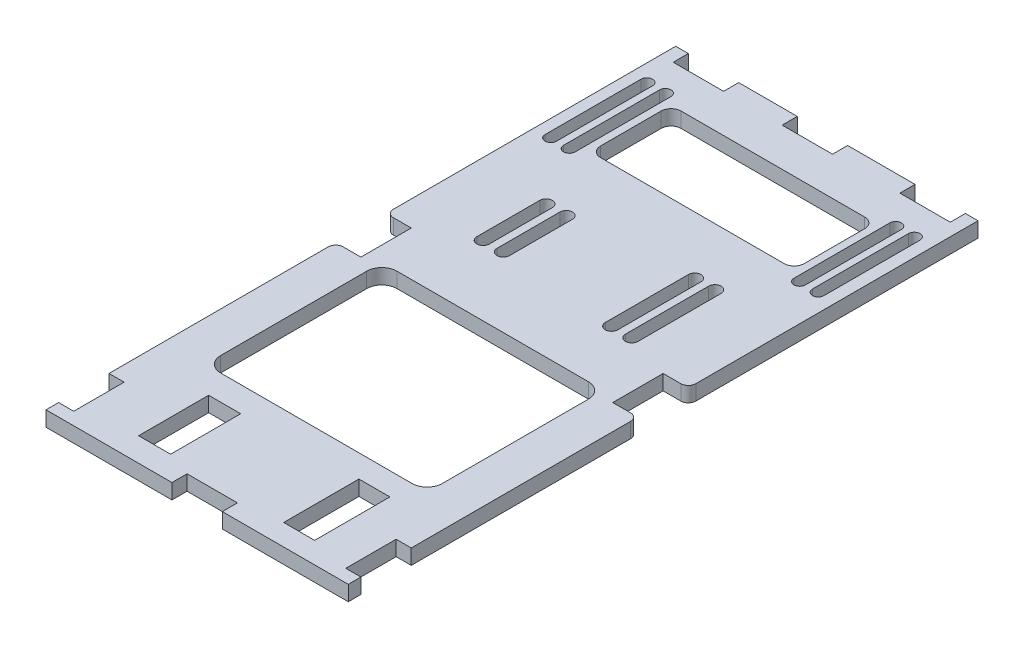
SolidWorks part; units mm, degrees
material "Acrílico (Impacto medio-alto)"
ref_plane "Alzado" through (0, 0, 0) normal (0, 0, 1) x (1, 0, 0)
ref_plane "Planta" through (0, 0, 0) normal (0, 1, 0) x (1, 0, 0)
ref_plane "Vista lateral" through (0, 0, 0) normal (1, 0, 0) x (0, 0, -1)
sketch "Croquis1" plane through (0, 0, 0) normal (0, 1, 0) x (1, 0, 0)
  line L0 (19.1085, -58.278) -> (19.1085, -43.3424) construction
  line L1 (-30, 62.5) -> (-27.5, 62.5)
  line L2 (-30, 62.5) -> (-30, 6.5)
  line L3 (-30, -62.5) -> (-5, -62.5)
  line L4 (30, 62.5) -> (30, 6.5)
  line L5 (-30, 62.5) -> (30, -62.5) construction
  line L6 (-30, -62.5) -> (30, 62.5) construction
  line L7 (19.1085, -43.3424) -> (12.9586, -43.3424) construction
  line L8 (12.9586, -43.3424) -> (12.9586, -58.278) construction
  line L9 (12.9586, -58.278) -> (19.1085, -58.278) construction
  line L10 (-16.3572, -43.8549) -> (-16.3572, -57.7655) construction
  line L11 (-16.3572, -57.7655) -> (-10, -57.7655) construction
  line L12 (-10, -43.8549) -> (-16.3572, -43.8549) construction
  line L13 (-10, -57.7655) -> (-10, -43.8549) construction
  line L14 (19.1085, -58.278) -> (19.1085, -43.3424)
  line L15 (19.1085, -43.3424) -> (12.9586, -43.3424)
  line L16 (12.9586, -43.3424) -> (12.9586, -58.278)
  line L17 (12.9586, -58.278) -> (19.1085, -58.278)
  line L18 (-16.3572, -43.8549) -> (-16.3572, -57.7655)
  line L19 (-16.3572, -57.7655) -> (-10, -57.7655)
  line L20 (-10, -43.8549) -> (-16.3572, -43.8549)
  line L21 (-10, -57.7655) -> (-10, -43.8549)
  line L22 (5, -59.5) -> (5, -62.5) construction
  line L23 (-5, -59.5) -> (-5, -62.5) construction
  line L24 (-5, -59.5) -> (5, -59.5) construction
  line L25 (5, -59.5) -> (5, -62.5)
  line L26 (-5, -59.5) -> (-5, -62.5)
  line L27 (-5, -59.5) -> (5, -59.5)
  line L28 (5, -62.5) -> (30, -62.5)
  line L29 (27.5, 59.5) -> (27.5, 62.5) construction
  line L30 (27.5, 59.5) -> (17.5, 59.5) construction
  line L31 (17.5, 59.5) -> (17.5, 62.5) construction
  line L32 (-17.5, 62.5) -> (-17.5, 59.5) construction
  line L33 (-27.5, 59.5) -> (-17.5, 59.5) construction
  line L34 (-27.5, 62.5) -> (-27.5, 59.5) construction
  line L35 (-25, 5) -> (-25, -5) construction
  line L36 (-25, -5) -> (-30, -5) construction
  line L37 (-30, 5) -> (-25, 5) construction
  line L38 (30, -5) -> (25, -5) construction
  line L39 (25, 5) -> (25, -5) construction
  line L40 (25, 5) -> (30, 5) construction
  line L41 (27.5, 59.5) -> (27.5, 62.5)
  line L42 (27.5, 59.5) -> (17.5, 59.5)
  line L43 (17.5, 59.5) -> (17.5, 62.5)
  line L44 (-17.5, 62.5) -> (-17.5, 59.5)
  line L45 (-27.5, 59.5) -> (-17.5, 59.5)
  line L46 (-27.5, 62.5) -> (-27.5, 59.5)
  line L47 (-25, 5) -> (-25, -5)
  line L48 (-25, -5) -> (-28.5, -5)
  line L49 (-28.5, 5) -> (-25, 5)
  line L50 (28.5, -5) -> (25, -5)
  line L51 (25, 5) -> (25, -5)
  line L52 (25, 5) -> (28.5, 5)
  line L53 (-17.5, 62.5) -> (-5.876, 62.5)
  line L54 (27.5, 62.5) -> (30, 62.5)
  line L55 (-30, -6.5) -> (-30, -50)
  line L56 (30, -6.5) -> (30, -50)
  line L57 (23.903, 34.3442) -> (23.903, 53.3942)
  line L58 (21.617, 34.3442) -> (21.617, 53.3942)
  line L59 (-21.817, 34.3442) -> (-21.817, 53.3942)
  line L60 (-24.103, 34.3442) -> (-24.103, 53.3942)
  line L61 (27.586, 34.3442) -> (27.586, 53.3942)
  line L62 (25.3, 34.3442) -> (25.3, 53.3942)
  line L63 (25.3, 34.9392) -> (25.3, 52.7992) construction
  line L64 (-25.5, 34.3442) -> (-25.5, 53.3942)
  line L65 (-27.786, 34.3442) -> (-27.786, 53.3942)
  line L66 (-25.5, 52.7992) -> (-25.5, 34.9392) construction
  line L67 (-10.5, 10.0118) -> (-10.5, 22.5118)
  line L68 (-13, 10.0118) -> (-13, 22.5118)
  line L69 (22, -35.8348) -> (22, -6.8348)
  line L70 (19, -3.8348) -> (-19, -3.8348)
  line L71 (13, 8.0118) -> (13, 24.5118)
  line L72 (-22, -6.8348) -> (-22, -35.8348)
  line L73 (-19, -38.8348) -> (19, -38.8348)
  line L75 (10.5, 8.0118) -> (10.5, 24.5118)
  line L76 (-14.5, 10.0118) -> (-14.5, 22.5118)
  line L77 (-17, 10.0118) -> (-17, 22.5118)
  line L79 (17, 8.0118) -> (17, 24.5118)
  line L80 (14.5, 8.0118) -> (14.5, 24.5118)
  line L89 (-20.317, 49.8942) -> (-20.317, 37.8942)
  line L90 (20.117, 49.8942) -> (20.117, 37.8942)
  line L91 (-30, -60) -> (-27, -60) construction
  line L92 (-27, -60) -> (-27, -50) construction
  line L93 (18.117, 51.8942) -> (-13.317, 51.8942)
  line L94 (-13.317, 51.8942) -> (-18.317, 51.8942)
  line L95 (-30, -50) -> (-27, -50) construction
  line L96 (-18.317, 35.8942) -> (18.117, 35.8942)
  line L97 (27, -60) -> (30, -60) construction
  line L98 (27, -60) -> (27, -50) construction
  line L99 (27, -50) -> (30, -50) construction
  line L100 (-5.876, 62.5) -> (-5.876, 59.5) construction
  line L101 (4.124, 62.5) -> (4.124, 59.5) construction
  line L102 (-5.876, 59.5) -> (4.124, 59.5) construction
  line L103 (-30, -60) -> (-27, -60)
  line L104 (-27, -60) -> (-27, -50)
  line L105 (-30, -50) -> (-27, -50)
  line L106 (27, -60) -> (30, -60)
  line L107 (27, -60) -> (27, -50)
  line L108 (27, -50) -> (30, -50)
  line L109 (-5.876, 62.5) -> (-5.876, 59.5)
  line L110 (4.124, 62.5) -> (4.124, 59.5)
  line L111 (-5.876, 59.5) -> (4.124, 59.5)
  line L112 (-30, -60) -> (-30, -62.5)
  line L113 (30, -60) -> (30, -62.5)
  line L114 (4.124, 62.5) -> (17.5, 62.5)
  arc A0 (22, -6.8348) -> (19, -3.8348) centre (19, -6.8348) ccw
  arc A1 (-22, -35.8348) -> (-19, -38.8348) centre (-19, -35.8348) ccw
  arc A2 (19, -38.8348) -> (22, -35.8348) centre (19, -35.8348) ccw
  arc A3 (-19, -3.8348) -> (-22, -6.8348) centre (-19, -6.8348) ccw
  circle A4 centre (-22.96, 53.3942) radius 1.143 construction
  circle A5 centre (-22.96, 34.3442) radius 1.143 construction
  circle A6 centre (22.76, 53.3942) radius 1.143 construction
  circle A7 centre (22.76, 34.3442) radius 1.143 construction
  arc A8 (-21.817, 53.3942) -> (-24.103, 53.3942) centre (-22.96, 53.3942) ccw
  arc A9 (-24.103, 34.3442) -> (-21.817, 34.3442) centre (-22.96, 34.3442) ccw
  arc A10 (23.903, 53.3942) -> (21.617, 53.3942) centre (22.76, 53.3942) ccw
  arc A11 (21.617, 34.3442) -> (23.903, 34.3442) centre (22.76, 34.3442) ccw
  arc A12 (27.586, 53.3942) -> (25.3, 53.3942) centre (26.443, 53.3942) ccw
  arc A13 (25.3, 34.3442) -> (27.586, 34.3442) centre (26.443, 34.3442) ccw
  arc A14 (-25.5, 53.3942) -> (-27.786, 53.3942) centre (-26.643, 53.3942) ccw
  arc A15 (-27.786, 34.3442) -> (-25.5, 34.3442) centre (-26.643, 34.3442) ccw
  circle A16 centre (11.75, 8.0118) radius 1.25 construction
  circle A17 centre (11.75, 24.5118) radius 1.25 construction
  circle A18 centre (-11.75, 22.5118) radius 1.25 construction
  circle A19 centre (-11.75, 10.0118) radius 1.25 construction
  arc A20 (10.5, 8.0118) -> (13, 8.0118) centre (11.75, 8.0118) ccw
  arc A21 (13, 24.5118) -> (10.5, 24.5118) centre (11.75, 24.5118) ccw
  arc A22 (-10.5, 22.5118) -> (-13, 22.5118) centre (-11.75, 22.5118) ccw
  arc A23 (-13, 10.0118) -> (-10.5, 10.0118) centre (-11.75, 10.0118) ccw
  arc A24 (-14.5, 22.5118) -> (-17, 22.5118) centre (-15.75, 22.5118) ccw
  arc A25 (-17, 10.0118) -> (-14.5, 10.0118) centre (-15.75, 10.0118) ccw
  arc A26 (14.5, 8.0118) -> (17, 8.0118) centre (15.75, 8.0118) ccw
  arc A27 (17, 24.5118) -> (14.5, 24.5118) centre (15.75, 24.5118) ccw
  arc A33 (20.117, 49.8942) -> (18.117, 51.8942) centre (18.117, 49.8942) ccw
  arc A34 (20.117, 37.8942) -> (18.117, 35.8942) centre (18.117, 37.8942) cw
  arc A36 (-20.317, 37.8942) -> (-18.317, 35.8942) centre (-18.317, 37.8942) ccw
  arc A37 (-18.317, 51.8942) -> (-20.317, 49.8942) centre (-18.317, 49.8942) ccw
  arc A38 (-28.5, -5) -> (-30, -6.5) centre (-28.5, -6.5) ccw
  arc A39 (-28.5, 5) -> (-30, 6.5) centre (-28.5, 6.5) cw
  arc A40 (28.5, -5) -> (30, -6.5) centre (28.5, -6.5) cw
  arc A41 (30, 6.5) -> (28.5, 5) centre (28.5, 6.5) cw
  point P0 (0, 0)
  point P100 (0, 0)
  point P116 (-20.317, 35.8942)
  point P120 (-20.317, 51.8942)
  dimension "D3" = 3
  dimension "D15" = 2
  dimension "D16" = 1.5
  dimension "D1" = 60
  dimension "D2" = 125
  dimension "D4" = 35
  dimension "D5" = 8
  dimension "D6" = 8
  dimension "D7" = 1.5
  dimension "D8" = 2.5
  dimension "D9" = 2.5
  dimension "D10" = 1.5
  dimension "D11" = 16
  dimension "D12" = 1.5
  dimension "D13" = 1.5
  dimension "D14" = 1.5
extrude "Saliente-Extruir1" add sketch "Croquis1" along normal blind 3
